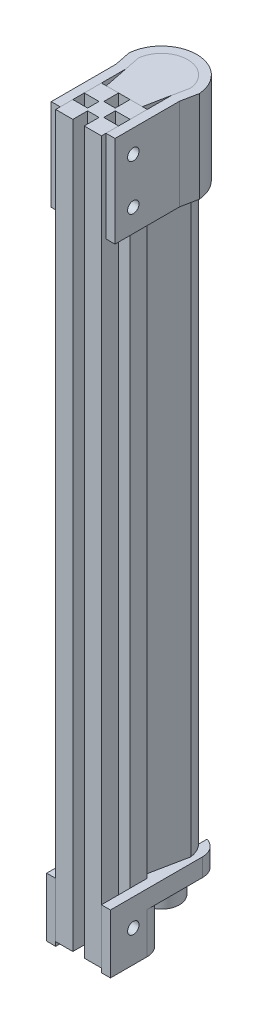
SolidWorks part; units mm, degrees
material "A286 Iron Base Superalloy"
ref_plane "Front Plane" through (0, 0, 0) normal (0, 0, 1) x (1, 0, 0)
ref_plane "Top Plane" through (0, 0, 0) normal (0, 1, 0) x (1, 0, 0)
ref_plane "Right Plane" through (0, 0, 0) normal (1, 0, 0) x (0, 0, -1)
sketch "Sketch1" plane through (0, 0, 0) normal (0, 1, 0) x (1, 0, 0)
  line L0 (14.4842, 1.795) -> (10, -20.605)
  line L1 (10, -20.605) -> (-10, -20.605)
  line L2 (-10, -20.605) -> (-14.4842, 1.795)
  line L3 (0, 14.595) -> (-46.807, 14.595) construction
  arc A0 (14.4842, 1.795) -> (-14.4842, 1.795) centre (0, 0) ccw
  point P10 (0, -20.605)
  dimension "D1" = 29.19
  dimension "D2" = 20
  dimension "D3" = 20.605
  dimension "D4" = 12.8
extrude "Boss-Extrude1" add sketch "Sketch1" along normal blind 369.57
sketch "Sketch2" plane through (0, 369.57, 0) normal (0, 1, 0) x (1, 0, 0)
  line L0 (-10, -20.605) -> (10, -20.605) construction
  line L1 (-12.7, -20.605) -> (12.7, -20.605)
  line L2 (-12.7, -20.605) -> (-12.7, -46.005)
  line L3 (-12.7, -46.005) -> (12.7, -46.005)
  line L4 (12.7, -20.605) -> (12.7, -46.005)
  point P8 (0, -20.605)
  point P9 (0, -20.605)
  dimension "D1" = 25.4
extrude "Boss-Extrude2" add sketch "Sketch2" against normal blind 400 separate body
sketch "Sketch7" plane through (0, 369.57, 0) normal (0, 1, 0) x (1, 0, 0)
  line L0 (12.7, -46.005) -> (12.7, -20.605) construction
  line L1 (12.7, -30.13) -> (4.5, -30.13)
  line L2 (12.7, -30.13) -> (12.7, -36.48)
  line L3 (12.7, -36.48) -> (4.5, -36.48)
  line L4 (4.5, -30.13) -> (4.5, -36.48)
  line L5 (0, -46.005) -> (0, 0) construction
  line L6 (-12.7, -46.005) -> (12.7, -46.005) construction
  line L7 (-12.7, -30.13) -> (-12.7, -36.48)
  line L8 (-12.7, -36.48) -> (-4.5, -36.48)
  line L9 (-4.5, -30.13) -> (-4.5, -36.48)
  line L10 (-12.7, -30.13) -> (-4.5, -30.13)
  line L11 (-10, -20.605) -> (10, -20.605) construction
  line L12 (-3.175, -20.605) -> (3.175, -20.605)
  line L13 (-3.175, -20.605) -> (-3.175, -28.805)
  line L14 (-3.175, -28.805) -> (3.175, -28.805)
  line L15 (3.175, -20.605) -> (3.175, -28.805)
  line L16 (-12.7, -33.305) -> (12.7, -33.305) construction
  line L17 (-3.175, -37.805) -> (3.175, -37.805)
  line L18 (3.175, -46.005) -> (3.175, -37.805)
  line L19 (-3.175, -46.005) -> (3.175, -46.005)
  line L20 (-3.175, -46.005) -> (-3.175, -37.805)
  point P12 (12.7, -33.305)
  point P13 (12.7, -33.305)
  point P25 (0, -20.605)
  dimension "D1" = 6.35
  dimension "D2" = 8.2
  dimension "D3" = 8.2
  dimension "D4" = 6.35
extrude "Cut-Extrude3" cut sketch "Sketch7" against normal through all
sketch "Sketch8" plane through (0, 369.57, 0) normal (0, 1, 0) x (1, 0, 0)
  line L0 (-12.7, -43.48) -> (-12.7, -7.1176)
  line L1 (-12.7, -36.48) -> (-12.7, -46.005) construction
  line L2 (-14.4842, 1.795) -> (-10, -20.605) construction
  line L3 (-12.7, -7.1176) -> (-14.4842, 1.795)
  line L4 (14.4842, 1.795) -> (12.7, -7.1176)
  line L5 (10, -20.605) -> (14.4842, 1.795) construction
  line L6 (12.7, -7.1176) -> (12.7, -43.48)
  line L7 (12.7, -46.005) -> (12.7, -36.48) construction
  line L8 (-17.7, -43.48) -> (-17.7, -7.6132)
  line L9 (-17.7, -7.6132) -> (-19.5338, 1.5473)
  line L10 (19.5338, 1.5473) -> (17.7, -7.6132)
  line L11 (17.7, -7.6132) -> (17.7, -43.48)
  line L12 (-17.7, -43.48) -> (-12.7, -43.48)
  line L13 (12.7, -43.48) -> (17.7, -43.48)
  line L14 (-12.7, -36.48) -> (-4.5, -36.48) construction
  arc A0 (-14.4842, 1.795) -> (14.4842, 1.795) centre (0, 0) cw
  arc A1 (14.4842, 1.795) -> (-14.4842, 1.795) centre (0, 0) ccw construction
  arc A2 (-19.5338, 1.5473) -> (19.5338, 1.5473) centre (0, 0) cw
  dimension "D1" = 5
  dimension "D2" = 7
extrude "Boss-Extrude3" add sketch "Sketch8" against normal blind 50.8 separate body
sketch "Sketch9" plane through (-17.7, 0, 0) normal (-1, 0, 0) x (0, 0, 1)
  line L0 (43.48, 344.17) -> (-19.595, 344.17) construction
  line L1 (43.48, 318.77) -> (43.48, 369.57) construction
  line L2 (-19.595, 369.57) -> (-19.595, 318.77) construction
  line L3 (36.48, -30.43) -> (36.48, 369.57) construction
  line L5 (7.6132, 369.57) -> (43.48, 369.57) construction
  circle A0 centre (33.305, 356.87) radius 3.175
  circle A1 centre (33.305, 331.47) radius 3.175
  point P2 (34.9297, 356.4006)
  point P4 (36.6105, 359.5221)
  point P11 (0, 0)
  point P12 (0, 0)
  point P13 (0, 0)
  point P15 (33.2489, 331.4289)
  point P18 (0, 0)
  dimension "D1" = 6.35
  dimension "D2" = 12.7
extrude "Cut-Extrude4" cut sketch "Sketch9" against normal through all
sketch "Sketch10" plane through (0, 0, 0) normal (0, -1, 0) x (1, 0, 0)
  circle A0 centre (0, 0) radius 9.975
  dimension "D1" = 19.95
extrude "Boss-Extrude4" add sketch "Sketch10" along normal blind 24.4221
sketch "Sketch11" plane through (0, 0, 0) normal (0, -1, 0) x (1, 0, 0)
  line L0 (-10, 20.605) -> (10, 20.605) construction
  line L1 (-17.7, 10.605) -> (17.7, 10.605)
  line L2 (-17.7, 10.605) -> (-17.7, 20.605)
  line L3 (-17.7, 20.605) -> (17.7, 20.605)
  line L4 (17.7, 10.605) -> (17.7, 20.605)
  point P6 (0, 20.605)
  dimension "D1" = 10
  dimension "D2" = 35.4
extrude "Boss-Extrude5" add sketch "Sketch11" along normal blind 10 separate body
sketch "Sketch12" plane through (0, -10, 0) normal (0, -1, 0) x (1, 0, 0)
  line L1 (-17.7, 20.605) -> (17.7, 20.605)
  line L2 (-17.7, 20.605) -> (-17.7, 15.605)
  line L3 (-17.7, 15.605) -> (17.7, 15.605)
  line L4 (17.7, 20.605) -> (17.7, 15.605)
  line L5 (17.7, 10.605) -> (17.7, 20.605) construction
  dimension "D1" = 5
  dimension "D2" = 35.4
extrude "Boss-Extrude6" add sketch "Sketch12" along normal blind 22.7
sketch "Sketch14" plane through (0, 0, 15.605) normal (0, 0, -1) x (-1, 0, 0)
  line L0 (17.7, -10) -> (-17.7, -10) construction
  circle A0 centre (0, -15) radius 3.175
  point P2 (0, 0)
  point P4 (0, 0)
  dimension "D1" = 6.35
  dimension "D2" = 5
extrude "Cut-Extrude5" cut sketch "Sketch14" against normal through all
sketch "Sketch15" plane through (0, 0, 20.605) normal (0, 0, 1) x (1, 0, 0)
  line L0 (-12.7, -30.43) -> (-12.7, 369.57) construction
  line L1 (-17.7, 0) -> (-12.7, 0)
  line L2 (-17.7, 0) -> (-17.7, -32.7)
  line L3 (-17.7, -32.7) -> (-12.7, -32.7)
  line L4 (-12.7, 0) -> (-12.7, -32.7)
  line L5 (17.7, -32.7) -> (-17.7, -32.7) construction
  line L6 (12.7, -30.43) -> (12.7, 369.57) construction
  line L7 (12.7, 0) -> (17.7, 0)
  line L8 (12.7, 0) -> (12.7, -32.7)
  line L9 (12.7, -32.7) -> (17.7, -32.7)
  line L10 (17.7, 0) -> (17.7, -32.7)
  line L11 (17.7, 0) -> (-17.7, 0) construction
extrude "Boss-Extrude7" add sketch "Sketch15" along normal blind 25.4
sketch "Sketch16" plane through (17.7, 0, 0) normal (1, 0, 0) x (0, 0, -1)
  line L2 (-10.605, -10) -> (-15.605, -10) construction
  line L3 (-30.13, -30.43) -> (-30.13, 331.47) construction
  circle A0 centre (-33.305, -15) radius 3.175
  point P4 (-31.7804, -14.4988)
  dimension "D1" = 6.35
  dimension "D2" = 5
extrude "Cut-Extrude6" cut sketch "Sketch16" against normal through all
sketch "Sketch17" plane through (0, 0, 10.605) normal (0, 0, -1) x (-1, 0, 0)
  line L1 (17.7, -10) -> (10.475, -10)
  line L2 (17.7, -10) -> (17.7, 0)
  line L3 (17.7, 0) -> (10.475, 0)
  line L4 (10.475, -10) -> (10.475, 0)
  line L5 (9.975, -24.4221) -> (9.975, 0) construction
  line L6 (0, -32.7) -> (0, 0) construction
  line L7 (17.7, -32.7) -> (-17.7, -32.7) construction
  line L8 (-17.7, 0) -> (-10.475, 0)
  line L9 (-10.475, -10) -> (-10.475, 0)
  line L10 (-17.7, -10) -> (-10.475, -10)
  line L11 (-17.7, -10) -> (-17.7, 0)
  line L12 (17.7, 0) -> (-17.7, 0) construction
  dimension "D1" = 0.5
extrude "Boss-Extrude8" add sketch "Sketch17" along normal blind 25.4
fillet "Fillet1" radius 10 4 edges at (17.7, -21.35, 15.605) (-17.7, -21.35, 15.605) (17.7, -5, -14.795) (-17.7, -5, -14.795)
